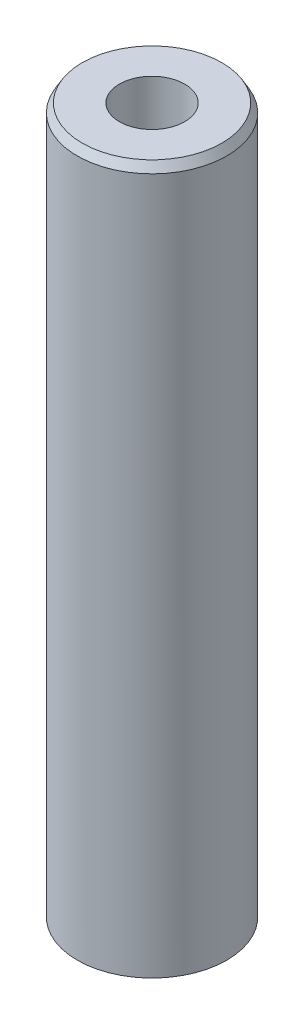
SolidWorks part; units mm, degrees
ref_plane "Front Plane" through (0, 0, 0) normal (0, 0, 1) x (1, 0, 0)
ref_plane "Top Plane" through (0, 0, 0) normal (0, 1, 0) x (1, 0, 0)
ref_plane "Right Plane" through (0, 0, 0) normal (1, 0, 0) x (0, 0, -1)
sketch "Sketch1" plane through (0, 0, 0) normal (0, 1, 0) x (1, 0, 0)
  circle A0 centre (0, 0) radius 45
  dimension "SHAFT_OD" = 90
extrude "Boss-Extrude1" add sketch "Sketch1" along normal blind 427.4033
sketch "Sketch2" plane through (0, 0, 0) normal (0, 1, 0) x (1, 0, 0)
  circle A0 centre (0, 0) radius 19.651
  dimension "BORE_D" = 39.3019
extrude "Cut-Extrude1" cut sketch "Sketch2" along normal through all
chamfer "Chamfer1" distance 5.1861 angle 30 2 edges at (0, 427.4033, 45) (0, 0, 45) first distance on face at (0, 427.4033, 45) first distance on face at (0, 0, 19.651)
